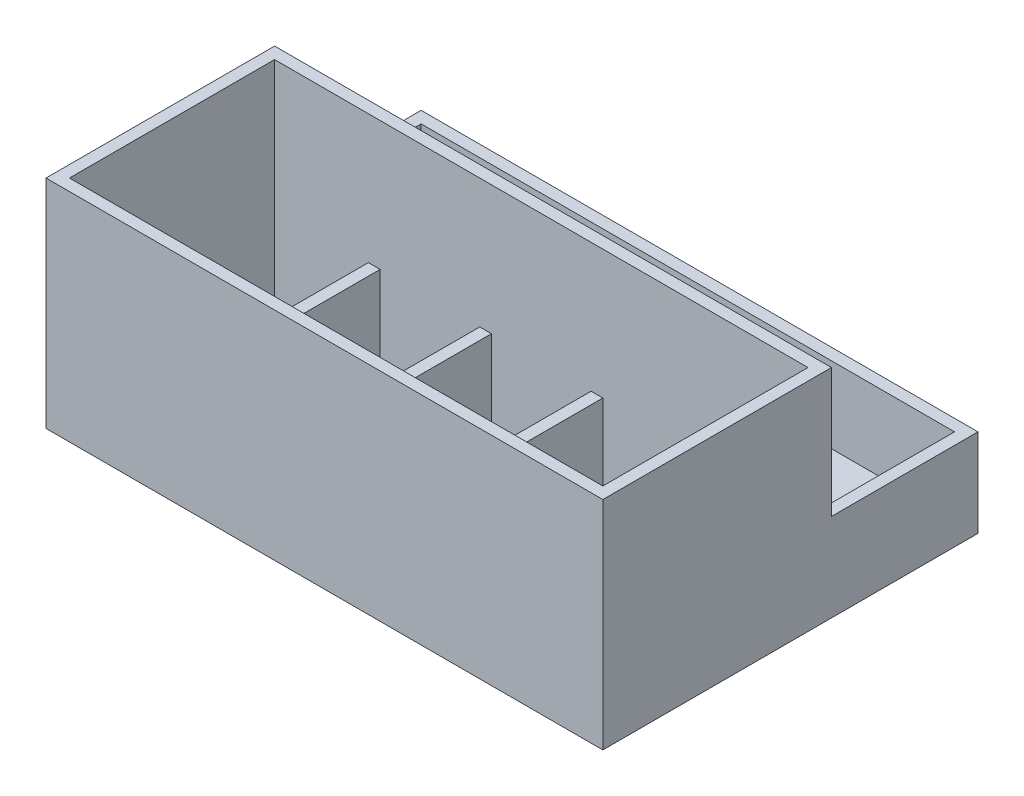
SolidWorks part; units mm, degrees
ref_plane "Front Plane" through (0, 0, 0) normal (0, 0, 1) x (1, 0, 0)
ref_plane "Top Plane" through (0, 0, 0) normal (0, 1, 0) x (1, 0, 0)
ref_plane "Right Plane" through (0, 0, 0) normal (1, 0, 0) x (0, 0, -1)
sketch "Sketch1" plane through (0, 0, 0) normal (0, 1, 0) x (1, 0, 0)
  line L5 (-47.5, 32) -> (47.5, 32)
  line L6 (-47.5, 32) -> (-47.5, -32)
  line L7 (-47.5, -32) -> (47.5, -32)
  line L8 (47.5, 32) -> (47.5, -32)
  line L9 (-47.5, 32) -> (47.5, -32) construction
  line L10 (-47.5, -32) -> (47.5, 32) construction
  point P4 (0, 0)
  point P5 (0, 0)
  dimension "D1" = 95
  dimension "D2" = 64
extrude "Boss-Extrude1" add sketch "Sketch1" along normal blind 2
sketch "Sketch2" plane through (0, 2, 0) normal (0, 1, 0) x (1, 0, 0)
  line L0 (-47.5, 32) -> (-28.5, 32) construction
  line L1 (47.5, 32) -> (-47.5, 32) construction
  line L2 (-28.5, 32) -> (-9.5, 32) construction
  line L3 (-9.5, 32) -> (9.5, 32) construction
  line L4 (9.5, 32) -> (28.5, 32) construction
  line L5 (28.5, 32) -> (47.5, 32) construction
  line L6 (-28.5, 32) -> (-28.5, -32) construction
  line L7 (-47.5, -32) -> (47.5, -32) construction
  line L8 (-28.5, -32) -> (-9.5, -32) construction
  line L9 (-9.5, -32) -> (-9.5, 32) construction
  line L10 (-47.5, -32) -> (-47.5, 7) construction
  line L11 (9.5, -32) -> (9.5, 32) construction
  line L12 (-47.5, 32) -> (-47.5, -32) construction
  line L13 (28.5, -32) -> (28.5, 32) construction
  line L14 (-47.5, 7) -> (47.5, 7) construction
  line L15 (47.5, -32) -> (47.5, 32) construction
  line L17 (-47.5, -12.5) -> (-28.5, -12.5) construction
  line L18 (-28.5, -12.5) -> (-9.5, -12.5) construction
  line L19 (-9.5, -12.5) -> (9.5, -12.5) construction
  line L20 (9.5, -12.5) -> (28.5, -12.5) construction
  line L21 (28.5, -12.5) -> (47.5, -12.5) construction
  circle A0 centre (-38, -12.5) radius 6.15
  circle A1 centre (-19, -12.5) radius 6.15
  circle A2 centre (0, -12.5) radius 6.15
  circle A3 centre (38, -12.5) radius 6.15
  dimension "D2" = 12.3
  dimension "D1" = 39
sketch "Sketch3" plane through (0, 2, -2) normal (0, -1, 0) x (1, 0, 0)
  line L3 (28.5, 14.5) -> (47.5, 14.5) construction
  line L4 (9.5, 14.5) -> (28.5, 14.5) construction
  line L5 (-9.5, 14.5) -> (9.5, 14.5) construction
  line L6 (-28.5, 14.5) -> (-9.5, 14.5) construction
  line L8 (-47.5, 14.5) -> (-28.5, 14.5) construction
  line L9 (-47.5, -5) -> (47.5, -5) construction
  line L10 (28.5, 34) -> (28.5, -30) construction
  line L11 (9.5, 34) -> (9.5, -30) construction
  line L13 (-47.5, 34) -> (-47.5, -5) construction
  line L14 (-9.5, 34) -> (-9.5, -30) construction
  line L17 (-28.5, 34) -> (-9.5, 34) construction
  line L18 (-28.5, -30) -> (-28.5, 34) construction
  line L19 (28.5, -30) -> (47.5, -30) construction
  line L20 (9.5, -30) -> (28.5, -30) construction
  line L21 (-9.5, -30) -> (9.5, -30) construction
  line L22 (-28.5, -30) -> (-9.5, -30) construction
  line L23 (-47.5, -30) -> (-28.5, -30) construction
  circle A8 centre (38, 14.5) radius 6.15
  circle A9 centre (0, 14.5) radius 6.15
  circle A10 centre (-19, 14.5) radius 6.15
  circle A11 centre (-38, 14.5) radius 6.15
  point P3 (0, 0)
extrude "Cut-Extrude1" cut sketch "Sketch3" along normal up to surface (2 mm away) up to face at (0, 0, 0)
sketch "Sketch4" plane through (0, 2, 0) normal (0, 1, 0) x (1, 0, 0)
  line L1 (-47.5, 32) -> (47.5, 32)
  line L2 (-47.5, 32) -> (-47.5, -32)
  line L3 (-47.5, -32) -> (47.5, -32)
  line L4 (47.5, 32) -> (47.5, -32)
extrude "Extrude-Thin1" add sketch "Sketch4" along normal blind 13 thin thin type one direction reverse wall 2
sketch "Sketch5" plane through (0, 15, 0) normal (0, 1, 0) x (1, 0, 0)
  line L1 (-47.5, -32) -> (47.5, -32)
  line L2 (-47.5, -32) -> (-47.5, 7)
  line L3 (-47.5, 7) -> (47.5, 7)
  line L4 (47.5, -32) -> (47.5, 7)
extrude "Extrude-Thin2" add sketch "Sketch5" along normal blind 22 thin thin type one direction reverse wall 2
sketch "Sketch6" plane through (0, 2, 0) normal (0, 1, 0) x (1, 0, 0)
  line L0 (-45.5, 7) -> (-29.5, 7)
  line L1 (-47.5, 7) -> (47.5, 7) construction
  line L2 (45.5, 7) -> (45.5, 5)
  line L3 (45.5, 5) -> (29.5, 5)
  line L4 (-45.5, 5) -> (-45.5, 7)
  line L5 (-28.5, 32) -> (-28.5, -32) construction
  line L6 (28.5, -32) -> (28.5, 32) construction
  line L7 (-29.5, 7) -> (-27.5, 7)
  line L8 (-29.5, 5) -> (-29.5, -30)
  line L9 (-45.5, -30) -> (45.5, -30) construction
  line L10 (-29.5, -30) -> (-27.5, -30)
  line L11 (-27.5, -30) -> (-27.5, 5)
  line L13 (-27.5, 7) -> (45.5, 7)
  line L14 (-10.5, 5) -> (-10.5, -30)
  line L15 (-10.5, -30) -> (-8.5, -30)
  line L16 (-8.5, -30) -> (-8.5, 5)
  line L18 (-9.5, -32) -> (-9.5, 32) construction
  line L19 (-45.5, -30) -> (45.5, -30) construction
  line L20 (9.5, -32) -> (9.5, 32) construction
  line L21 (8.5, 5) -> (8.5, -30)
  line L22 (8.5, -30) -> (10.5, -30)
  line L23 (10.5, -30) -> (10.5, 5)
  line L25 (27.5, 5) -> (27.5, -30)
  line L26 (27.5, -30) -> (29.5, -30)
  line L27 (29.5, -30) -> (29.5, 5)
  line L29 (-29.5, 5) -> (-45.5, 5)
  line L30 (-10.5, 5) -> (-27.5, 5)
  line L31 (8.5, 5) -> (-8.5, 5)
  line L32 (27.5, 5) -> (10.5, 5)
  line L33 (-45.5, 5) -> (-45.5, -30) construction
  line L34 (45.5, -30) -> (45.5, 5) construction
  point P5 (-28.5, 7)
  point P10 (-9.4975, 7)
  point P13 (9.6372, 7)
  point P14 (28.5, 7)
  point P20 (-28.5, 7)
  point P30 (9.5, -30)
  point P31 (-9.5, -30)
  point P32 (28.5, -30)
  point P39 (-9.5, -30)
  point P44 (9.5, -30)
  point P49 (28.5, -30)
  dimension "D1" = 2
  dimension "D2" = 2
  dimension "D3" = 2
  dimension "D4" = 2
extrude "Boss-Extrude5" add sketch "Sketch6" along normal up to surface (13 mm away) up to face at (0, 15, -6)
